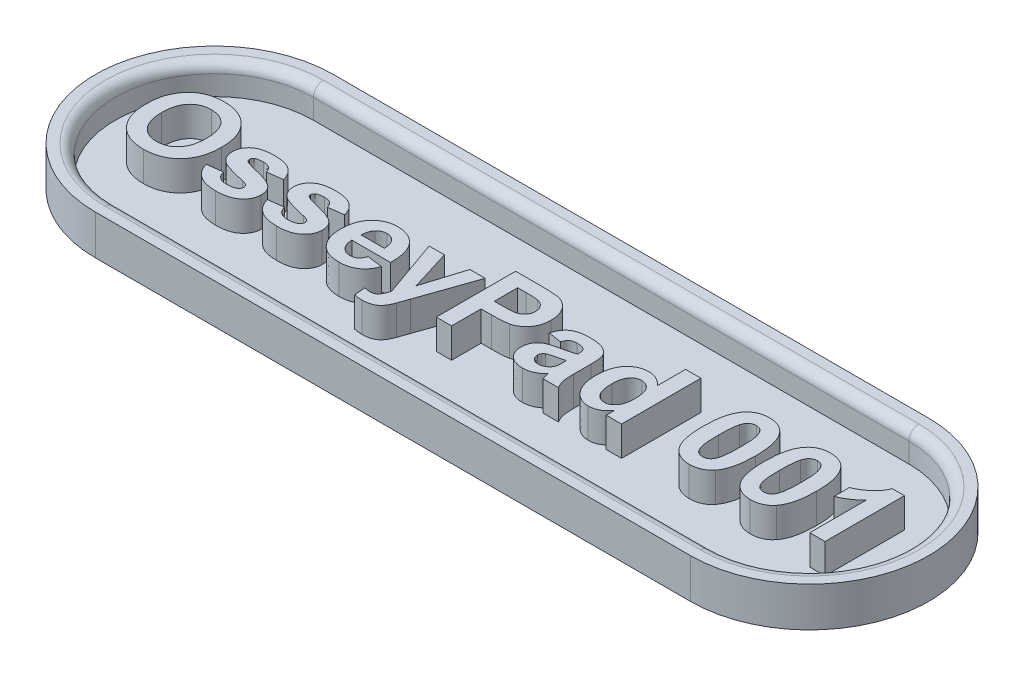
SolidWorks part; units mm, degrees
material "ABS PC"
ref_plane "Front Plane" through (0, 0, 0) normal (0, 0, 1) x (1, 0, 0)
ref_plane "Top Plane" through (0, 0, 0) normal (0, 1, 0) x (1, 0, 0)
ref_plane "Right Plane" through (0, 0, 0) normal (1, 0, 0) x (0, 0, -1)
sketch "Sketch1" plane through (0, 0, 0) normal (0, 1, 0) x (1, 0, 0)
  line L0 (-15, 0) -> (15, 0) construction
  line L1 (-15, 6) -> (15, 6)
  line L2 (-15, -6) -> (15, -6)
  arc A0 (-15, 6) -> (-15, -6) centre (-15, 0) ccw
  arc A1 (15, -6) -> (15, 6) centre (15, 0) ccw
  point P2 (0, 0)
  dimension "D1" = 12
  dimension "D2" = 30
extrude "Boss-Extrude1" add sketch "Sketch1" along normal blind 2
sketch "Sketch2" plane through (0, 2, 0) normal (0, 1, 0) x (1, 0, 0)
  line L0 (-15, 0) -> (15, 0) construction
  line L1 (-15, 5) -> (15, 5)
  line L2 (-15, -5) -> (15, -5)
  arc A0 (-15, 5) -> (-15, -5) centre (-15, 0) ccw
  arc A1 (15, -5) -> (15, 5) centre (15, 0) ccw
  point P2 (0, 0)
  dimension "D1" = 30
  dimension "D2" = 10
extrude "Cut-Extrude1" cut sketch "Sketch2" against normal blind 1.5
sketch "Sketch3" plane through (0, 0.5, 0) normal (0, 1, 0) x (1, 0, 0)
  line L0 (-21, -1.995) -> (21, -1.995) construction
  line L1 (0, -8.7006) -> (0, 6.9821) construction
  line L3 (-15, -5) -> (15, -5) construction
  text T0 "OsseyPad 001" font "Arial" height 4
  dimension "D1" = 3.005
extrude "Boss-Extrude2" add sketch "Sketch3" along normal blind 1.5
fillet "Fillet1" radius 0.5 4 edges at (0, 2, -5) (20, 2, 0) (0, 2, 5) (-20, 2, 0)
